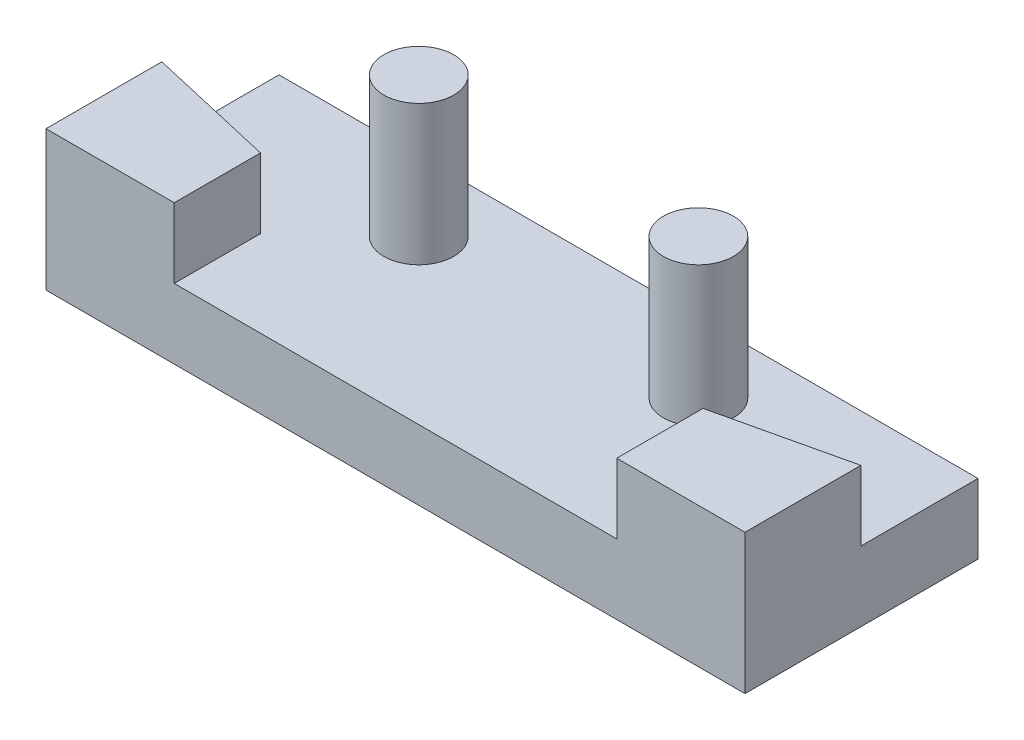
SolidWorks part; units mm, degrees
ref_plane "Front Plane" through (0, 0, 0) normal (0, 0, 1) x (1, 0, 0)
ref_plane "Top Plane" through (0, 0, 0) normal (0, 1, 0) x (1, 0, 0)
ref_plane "Right Plane" through (0, 0, 0) normal (1, 0, 0) x (0, 0, -1)
sketch "Sketch2" plane through (0, 0, 0) normal (0, 1, 0) x (1, 0, 0)
  line L1 (0, 0) -> (30, 0)
  line L2 (0, 0) -> (0, -10)
  line L3 (0, -10) -> (30, -10)
  line L4 (30, 0) -> (30, -10)
  dimension "D1" = 30
  dimension "D2" = 10
extrude "Boss-Extrude2" add sketch "Sketch2" along normal blind 6
sketch "Sketch4" plane through (0, 6, 0) normal (0, 1, 0) x (1, 0, 0)
  line L0 (30, 0) -> (0, 0) construction
  line L1 (0, 0) -> (0, -10) construction
  line L2 (9, -3) -> (3.3125, -1.6869) construction
  line L3 (9, -3) -> (8.1002, -6.8975) construction
  line L4 (8.1002, -6.8975) -> (0, -5.0274) construction
  line L5 (0, -5.0274) -> (5.5043, -6.2982)
  line L6 (5.5043, -6.2982) -> (5.5043, -10)
  line L7 (0, -10) -> (30, -10) construction
  line L8 (5.5043, -10) -> (24.4957, -10)
  line L9 (0, -5.0274) -> (0, 0)
  line L10 (0, 0) -> (30, 0)
  line L11 (15, 0) -> (15, -10) construction
  line L12 (30, -5.0274) -> (30, 0)
  line L13 (24.4957, -6.2982) -> (24.4957, -10)
  line L14 (30, -5.0274) -> (24.4957, -6.2982)
  circle A0 centre (9, -3) radius 1.5
  circle A1 centre (21, -3) radius 1.5
  dimension "D1" = 3
  dimension "D3" = 3
  dimension "D2" = 3
  dimension "D4" = 12
  dimension "D5" = 9
  dimension "D6" = 3
  dimension "D7" = 13
  dimension "D8" = 4
  dimension "D9" = 90
extrude "Cut-Extrude1" cut sketch "Sketch4" against normal blind 3 contours L5 L6 L8 L13 L14 L12 L10 L9
extrude "Boss-Extrude4" add sketch "Sketch4<4>" along normal blind 3 separate body contours A0 | A1 region at (9, 6, 3) region at (21, 6, 3)
sketch "Sketch4<4>" plane through (0, 6, 0) normal (0, 1, 0) x (1, 0, 0) same geometry as "Sketch4"
extrude "Boss-Extrude5" add sketch "Sketch4<5>" against normal blind 3 contours A0 | A1
sketch "Sketch4<5>" plane through (0, 6, 0) normal (0, 1, 0) x (1, 0, 0) same geometry as "Sketch4"
